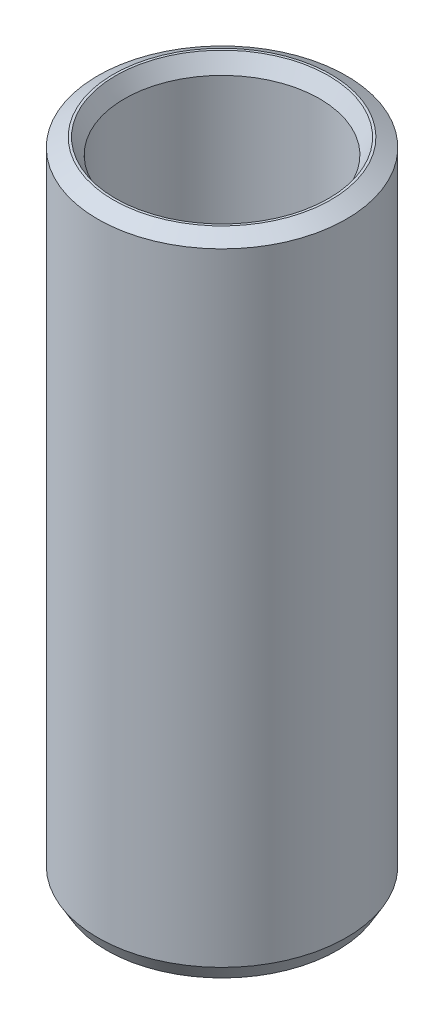
SolidWorks part; units mm, degrees
ref_plane "Front Plane" through (0, 0, 0) normal (0, 0, 1) x (1, 0, 0)
ref_plane "Top Plane" through (0, 0, 0) normal (0, 1, 0) x (1, 0, 0)
ref_plane "Right Plane" through (0, 0, 0) normal (1, 0, 0) x (0, 0, -1)
sketch "Sketch1" plane through (0, 0, 0) normal (0, 1, 0) x (1, 0, 0)
  circle A0 centre (0, 0) radius 35
  dimension "SLEEVE_OD" = 70
extrude "Boss-Extrude1" add sketch "Sketch1" along normal blind 182.0955
sketch "Sketch2" plane through (0, 0, 0) normal (0, 1, 0) x (1, 0, 0)
  circle A0 centre (0, 0) radius 27.4625
  dimension "BORE_D" = 54.9249
extrude "Cut-Extrude1" cut sketch "Sketch2" along normal through all
chamfer "Chamfer1" distance 2.5185 angle 60 4 edges at (0, 182.0955, 27.4625) (0, 0, 27.4625) (0, 0, 35) (0, 182.0955, 35) first distance on face at (0, 182.0955, 27.4625) first distance on face at (0, 0, 27.4625) first distance on face at (0, 182.0955, 35)
